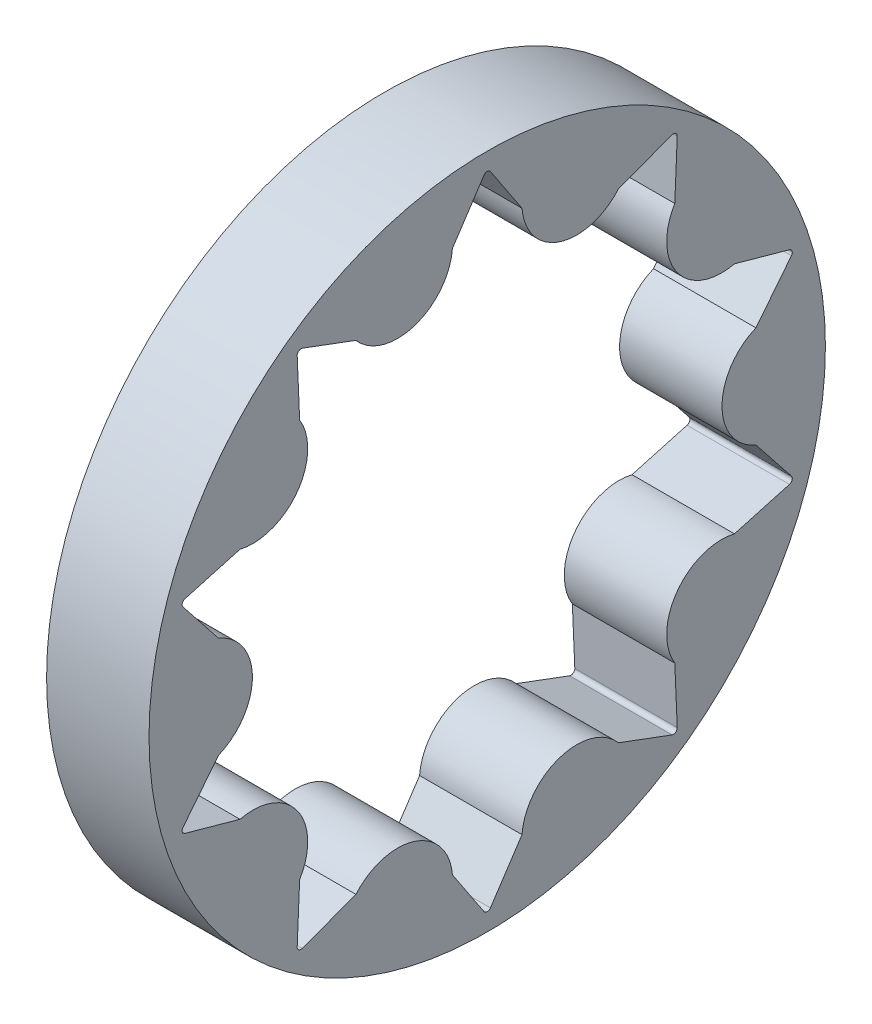
SolidWorks part; units mm, degrees
ref_plane "Front Plane" through (0, 0, 0) normal (0, 0, 1) x (1, 0, 0)
ref_plane "Top Plane" through (0, 0, 0) normal (0, 1, 0) x (1, 0, 0)
ref_plane "Right Plane" through (0, 0, 0) normal (1, 0, 0) x (0, 0, -1)
sketch "Sketch1" plane through (0, 0, 0) normal (1, 0, 0) x (0, 0, -1)
  line L0 (0, 0) -> (0, 16.75)
  line L1 (0, 0) -> (9.8454, 13.551)
  line L2 (0, 16.75) -> (1.8002, 14.035)
  line L3 (6.7932, 12.4127) -> (9.8454, 13.551)
  circle A0 centre (0, 0) radius 12.15
  circle A1 centre (0, 0) radius 16.75
  circle A2 centre (0, 0) radius 14.15 construction
  arc A3 (1.8002, 14.035) -> (6.7932, 12.4127) centre (4.6325, 14.2573) ccw
  dimension "D1" = 24.3
  dimension "D2" = 33.5
  dimension "D3" = 2.6
  dimension "D4" = 36
  dimension "D5" = 5.25
extrude "Boss-Extrude1" add sketch "Sketch1" along normal blind 5.3 contours L1 A0 L0 | A3 A0 L1 L3 | A3 L2 L0 A0 region at (0, 7.5775, -2.4621) region at (0, 13.656, -0.9718) region at (0, 11.6191, -7.2406)
pattern_circular "CirPattern1" count 10 over 360 about axis through (5.3, 0, 0) along (-1, 0, 0) of "Boss-Extrude1" reverse direction yes
fillet "Fillet1" radius 0.2 1 edges at (2.65, 16.75, 0)
fillet "Fillet3" radius 0.2 9 edges at (2.65, 13.551, 9.8454) (2.65, 5.176, 15.9302) (2.65, -5.176, 15.9302) (2.65, -13.551, 9.8454) (2.65, -16.75, 0) (2.65, -13.551, -9.8454) (2.65, -5.176, -15.9302) (2.65, 5.176, -15.9302) (2.65, 13.551, -9.8454)
sketch "Sketch2" plane through (0, 0, 0) normal (-1, 0, 0) x (0, 0, 1)
  circle A0 centre (0, 0) radius 10
  circle A1 centre (0, 0) radius 4.05
  dimension "D1" = 20
  dimension "D2" = 8.1
extrude "Boss-Extrude2" add sketch "Sketch2" along normal blind 16.7
extrude "Cut-Extrude1" cut sketch "Sketch2<2>" against normal through all both and the other way through all contours A1 region at (0, 0, 0)
sketch "Sketch2<2>" plane through (0, 0, 0) normal (-1, 0, 0) x (0, 0, 1) same geometry as "Sketch2"
sketch "Sketch3" plane through (5.3, 0, 0) normal (1, 0, 0) x (0, 0, -1)
  circle A0 centre (0, 0) radius 17.5
  circle M1 centre (0, 0) radius 4.05
  line M2 (-6.7932, 12.4127) -> (-9.5628, 13.4456)
  arc M3 (-9.5628, 13.4456) -> (-9.8325, 13.2497) centre (-9.6327, 13.2582) ccw
  line M4 (-9.8325, 13.2497) -> (-9.7059, 10.2965)
  arc M5 (-9.7059, 10.2965) -> (-12.7918, 6.0491) centre (-12.128, 8.8115) cw
  line M6 (-12.7918, 6.0491) -> (-15.6396, 5.2569)
  arc M7 (-15.6396, 5.2569) -> (-15.7426, 4.9398) centre (-15.586, 5.0642) ccw
  line M8 (-15.7426, 4.9398) -> (-13.9044, 2.625)
  arc M9 (-13.9044, 2.625) -> (-13.9044, -2.625) centre (-14.991, 0) cw
  line M10 (-13.9044, -2.625) -> (-15.7426, -4.9398)
  arc M11 (-15.7426, -4.9398) -> (-15.6396, -5.2569) centre (-15.586, -5.0642) ccw
  line M12 (-15.6396, -5.2569) -> (-12.7918, -6.0491)
  arc M13 (-12.7918, -6.0491) -> (-9.7059, -10.2965) centre (-12.128, -8.8115) cw
  line M14 (-9.7059, -10.2965) -> (-9.8325, -13.2497)
  arc M15 (-9.8325, -13.2497) -> (-9.5628, -13.4456) centre (-9.6327, -13.2582) ccw
  line M16 (-9.5628, -13.4456) -> (-6.7932, -12.4127)
  arc M17 (-6.7932, -12.4127) -> (-1.8002, -14.035) centre (-4.6325, -14.2573) cw
  line M18 (-1.8002, -14.035) -> (-0.1667, -16.4986)
  arc M19 (-0.1667, -16.4986) -> (0.1667, -16.4986) centre (0, -16.3881) ccw
  line M20 (0.1667, -16.4986) -> (1.8002, -14.035)
  arc M21 (1.8002, -14.035) -> (6.7932, -12.4127) centre (4.6325, -14.2573) cw
  line M22 (6.7932, -12.4127) -> (9.5628, -13.4456)
  arc M23 (9.5628, -13.4456) -> (9.8325, -13.2497) centre (9.6327, -13.2582) ccw
  line M24 (9.8325, -13.2497) -> (9.7059, -10.2965)
  arc M25 (9.7059, -10.2965) -> (12.7918, -6.0491) centre (12.128, -8.8115) cw
  line M26 (12.7918, -6.0491) -> (15.6396, -5.2569)
  arc M27 (15.6396, -5.2569) -> (15.7426, -4.9398) centre (15.586, -5.0642) ccw
  line M28 (15.7426, -4.9398) -> (13.9044, -2.625)
  arc M29 (13.9044, -2.625) -> (13.9044, 2.625) centre (14.991, 0) cw
  line M30 (13.9044, 2.625) -> (15.7426, 4.9398)
  arc M31 (15.7426, 4.9398) -> (15.6396, 5.2569) centre (15.586, 5.0642) ccw
  line M32 (15.6396, 5.2569) -> (12.7918, 6.0491)
  arc M33 (12.7918, 6.0491) -> (9.7059, 10.2965) centre (12.128, 8.8115) cw
  line M34 (9.7059, 10.2965) -> (9.8325, 13.2497)
  arc M35 (9.8325, 13.2497) -> (9.5628, 13.4456) centre (9.6327, 13.2582) ccw
  line M36 (9.5628, 13.4456) -> (6.7932, 12.4127)
  arc M37 (6.7932, 12.4127) -> (1.8002, 14.035) centre (4.6325, 14.2573) cw
  line M38 (1.8002, 14.035) -> (0.1667, 16.4986)
  arc M39 (0.1667, 16.4986) -> (-0.1667, 16.4986) centre (0, 16.3881) ccw
  line M40 (-0.1667, 16.4986) -> (-1.8002, 14.035)
  arc M41 (-1.8002, 14.035) -> (-6.7932, 12.4127) centre (-4.6325, 14.2573) cw
  dimension "D1" = 35
extrude "Boss-Extrude3" add sketch "Sketch3" along normal blind 5.3 separate body contours M41 M2 M3 M4 M5 M6 M7 M8 M9 M10 M11 M12 M13 M14 M15 M16 M17 M18 M19 M20 M21 M22 M23 M24 M25 M26 M27 M28 M29 M30 M31 M32 M33 M34 M35 M36 M37 M38 M39 M40 M1 | A0 region at (5.3, 11.1198, 3.613)
extrude "Cut-Extrude2" cut sketch "Sketch3<3>" against normal through all
sketch "Sketch3<3>" plane through (5.3, 0, 0) normal (1, 0, 0) x (0, 0, -1) same geometry as "Sketch3"
